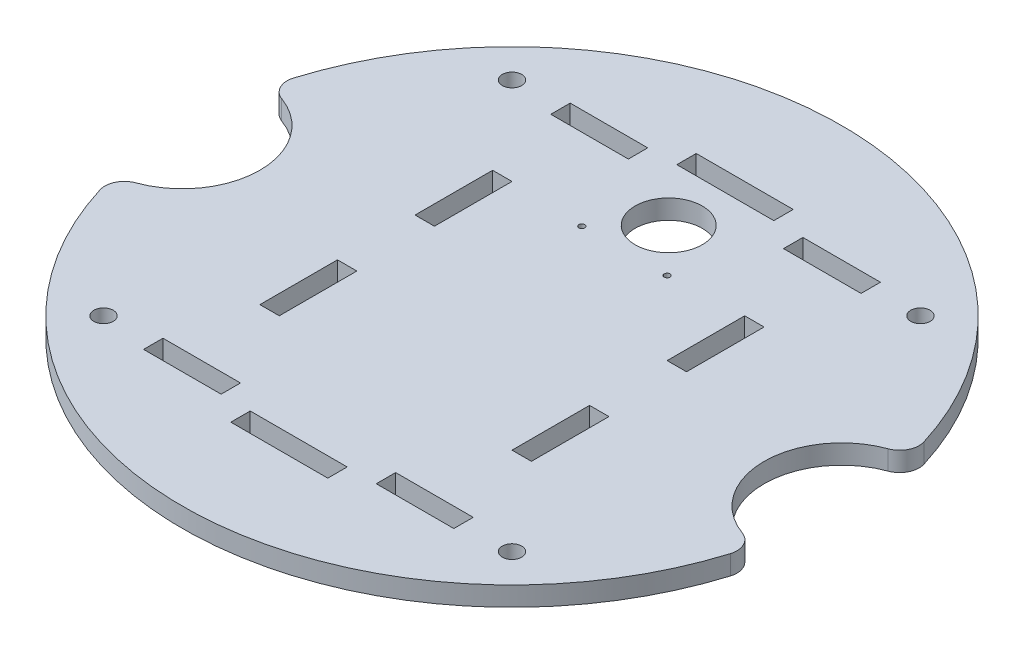
SolidWorks part; units mm, degrees
material "Pine"
ref_plane "Front Plane" through (0, 0, 0) normal (0, 0, 1) x (1, 0, 0)
ref_plane "Top Plane" through (0, 0, 0) normal (0, 1, 0) x (1, 0, 0)
ref_plane "Right Plane" through (0, 0, 0) normal (1, 0, 0) x (0, 0, -1)
sketch "Sketch1" plane through (0, 0, 0) normal (0, 1, 0) x (1, 0, 0)
  line L0 (0, 0) -> (0, 123.9148) construction
  line L1 (0, 0) -> (144.4711, 0) construction
  line L2 (-50.8, 63.5) -> (-25.4, 63.5)
  line L3 (-50.8, 63.5) -> (-50.8, 69.85)
  line L4 (-50.8, 69.85) -> (-25.4, 69.85)
  line L5 (-25.4, 63.5) -> (-25.4, 69.85)
  line L6 (25.4, 63.5) -> (25.4, 69.85)
  line L7 (50.8, 69.85) -> (25.4, 69.85)
  line L8 (50.8, 63.5) -> (50.8, 69.85)
  line L9 (50.8, 63.5) -> (25.4, 63.5)
  line L10 (-25.4, -63.5) -> (-25.4, -69.85)
  line L11 (-50.8, -63.5) -> (-25.4, -63.5)
  line L12 (-50.8, -63.5) -> (-50.8, -69.85)
  line L13 (-50.8, -69.85) -> (-25.4, -69.85)
  line L14 (50.8, -63.5) -> (50.8, -69.85)
  line L15 (50.8, -69.85) -> (25.4, -69.85)
  line L16 (25.4, -63.5) -> (25.4, -69.85)
  line L17 (50.8, -63.5) -> (25.4, -63.5)
  line L18 (38.1, -38.1) -> (44.45, -38.1)
  line L19 (38.1, 38.1) -> (44.45, 38.1)
  line L20 (38.1, 38.1) -> (38.1, 12.7)
  line L21 (38.1, 12.7) -> (44.45, 12.7)
  line L22 (44.45, 38.1) -> (44.45, 12.7)
  line L23 (38.1, -38.1) -> (38.1, -12.7)
  line L24 (38.1, -12.7) -> (44.45, -12.7)
  line L25 (44.45, -38.1) -> (44.45, -12.7)
  line L26 (-38.1, -38.1) -> (-44.45, -38.1)
  line L27 (-44.45, -38.1) -> (-44.45, -12.7)
  line L28 (-38.1, -38.1) -> (-38.1, -12.7)
  line L29 (-38.1, -12.7) -> (-44.45, -12.7)
  line L30 (-38.1, 12.7) -> (-44.45, 12.7)
  line L31 (-38.1, 38.1) -> (-38.1, 12.7)
  line L32 (-38.1, 38.1) -> (-44.45, 38.1)
  line L33 (-44.45, 38.1) -> (-44.45, 12.7)
  line L34 (-15.875, 69.85) -> (-15.875, 76.2)
  line L35 (15.875, -69.85) -> (-15.875, -69.85)
  line L36 (15.875, -69.85) -> (15.875, -76.2)
  line L37 (15.875, -76.2) -> (-15.875, -76.2)
  line L38 (-15.875, -69.85) -> (-15.875, -76.2)
  line L39 (15.875, -69.85) -> (-15.875, -76.2) construction
  line L40 (15.875, -76.2) -> (-15.875, -69.85) construction
  line L41 (15.875, 76.2) -> (-15.875, 76.2)
  line L42 (15.875, 69.85) -> (15.875, 76.2)
  line L43 (15.875, 69.85) -> (-15.875, 69.85)
  arc A0 (-103.1875, -31.7103) -> (103.1875, -31.7103) centre (0, 0) ccw
  circle A1 centre (0, 51.308) radius 10.9982
  arc A2 (-99.2841, -23.876) -> (-99.2841, 23.876) centre (-107.95, 0) ccw
  arc A3 (-99.2841, 23.876) -> (-103.1875, 31.7103) centre (-97.1176, 29.845) cw
  arc A4 (-99.2841, -23.876) -> (-103.1875, -31.7103) centre (-97.1176, -29.845) ccw
  arc A5 (99.2841, -23.876) -> (103.1875, -31.7103) centre (97.1176, -29.845) cw
  arc A6 (99.2841, -23.876) -> (99.2841, 23.876) centre (107.95, 0) cw
  arc A7 (99.2841, 23.876) -> (103.1875, 31.7103) centre (97.1176, 29.845) ccw
  arc A8 (103.1875, 31.7103) -> (-103.1875, 31.7103) centre (0, 0) ccw
  arc A9 (-25.2497, 52.1741) -> (-25.0774, 50.6465) centre (3.2211, 54.6124) ccw construction
  arc A11 (4.4749, 49.3063) -> (5.9938, 49.211) centre (5.3694, 51.4101) ccw construction
  circle A12 centre (13.97, 36.83) radius 0.9525
  circle A13 centre (-13.97, 36.83) radius 0.9525
  circle A14 centre (13.97, 36.83) radius 0.9525 construction
  point P52 (0, -73.025)
  point P61 (-25.1738, 51.4092)
  point P66 (5.2262, 49.1286)
  dimension "D1" = 215.9
  dimension "D10" = 21.9964
  dimension "D12" = 50.8
  dimension "D13" = 6.35
  dimension "D14" = 6.35
  dimension "D11" = 51.308
  dimension "D2" = 25.4
  dimension "D3" = 25.4
  dimension "D4" = 6.35
  dimension "D5" = 63.5
  dimension "D6" = 6.35
  dimension "D7" = 25.4
  dimension "D8" = 12.7
  dimension "D9" = 38.1
  dimension "D15" = 31.75
  dimension "D16" = 6.35
extrude "Boss-Extrude1" add sketch "Sketch1" along normal blind 6.35
sketch "Sketch2" plane through (0, 0, 0) normal (0, -1, 0) x (1, 0, 0)
  line L0 (0, 0) -> (0, 99.3828) construction
  line L1 (0, 0) -> (-150.0844, 0) construction
  circle A0 centre (-66.8782, 66.8782) radius 3.175
  circle A1 centre (66.8782, 66.8782) radius 3.175
  circle A2 centre (66.8782, -66.8782) radius 3.175
  circle A3 centre (-66.8782, -66.8782) radius 3.175
  dimension "D1" = 6.35
extrude "Cut-Extrude1" cut sketch "Sketch2" against normal up to surface (6.35 mm away) up to face at (0, 6.35, 73.025)
